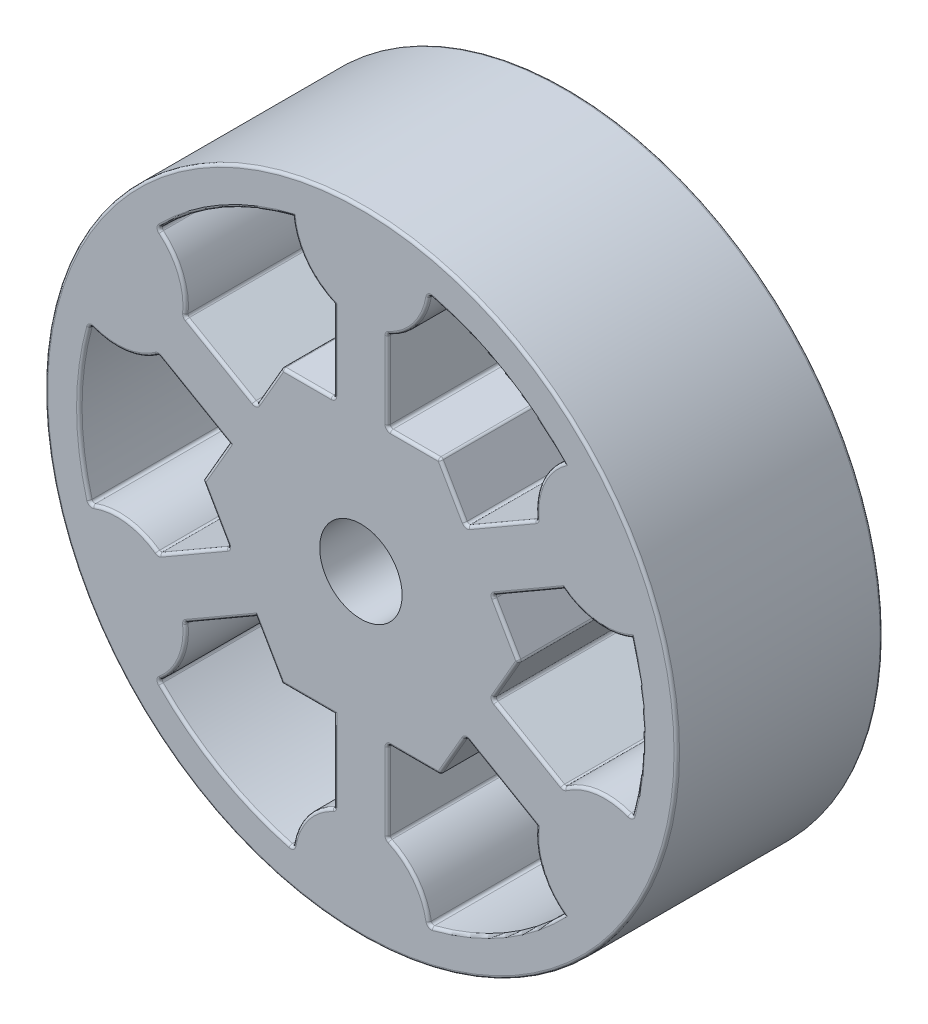
SolidWorks part; units mm, degrees
ref_plane "Front Plane" through (0, 0, 0) normal (0, 0, 1) x (1, 0, 0)
ref_plane "Top Plane" through (0, 0, 0) normal (0, 1, 0) x (1, 0, 0)
ref_plane "Right Plane" through (0, 0, 0) normal (1, 0, 0) x (0, 0, -1)
sketch "Sketch1" plane through (0, 0, 0) normal (0, 0, 1) x (1, 0, 0)
  line L0 (0, 1000) -> (0, -9.9593) construction
  line L1 (0, 0) -> (-7577.3498, 0) construction
  line L2 (-1.9562, 15.8986) -> (-1.9562, 9.9593)
  line L3 (11.5, 0) -> (9.6031, 3.2855)
  line L4 (5.75, 9.9593) -> (1.9562, 9.9593)
  line L5 (-5.75, 9.9593) -> (-7.6469, 6.6738)
  line L6 (-11.5, 0) -> (-9.6031, -3.2855)
  line L7 (-5.75, -9.9593) -> (-1.9562, -9.9593)
  line L8 (5.75, -9.9593) -> (7.6469, -6.6738)
  line L9 (1.9562, 15.8986) -> (1.9562, 9.9593)
  line L10 (14.7467, 6.2551) -> (9.6031, 3.2855)
  line L11 (12.7904, 9.6434) -> (7.6469, 6.6738)
  line L12 (5.75, -9.9593) -> (7.6469, -6.6738)
  line L13 (11.5, 0) -> (9.6031, 3.2855)
  line L14 (5.75, 9.9593) -> (1.9562, 9.9593)
  line L15 (-5.75, 9.9593) -> (-7.6469, 6.6738)
  line L16 (-11.5, 0) -> (-9.6031, -3.2855)
  line L17 (-5.75, -9.9593) -> (-1.9562, -9.9593)
  line L18 (12.7904, -9.6434) -> (7.6469, -6.6738)
  line L19 (14.7467, -6.2551) -> (9.6031, -3.2855)
  line L20 (-5.75, -9.9593) -> (-1.9562, -9.9593)
  line L21 (5.75, -9.9593) -> (7.6469, -6.6738)
  line L22 (11.5, 0) -> (9.6031, 3.2855)
  line L23 (5.75, 9.9593) -> (1.9562, 9.9593)
  line L24 (-5.75, 9.9593) -> (-7.6469, 6.6738)
  line L25 (-11.5, 0) -> (-9.6031, -3.2855)
  line L26 (-1.9562, -15.8986) -> (-1.9562, -9.9593)
  line L27 (1.9562, -15.8986) -> (1.9562, -9.9593)
  line L28 (-11.5, 0) -> (-9.6031, -3.2855)
  line L29 (-5.75, -9.9593) -> (-1.9562, -9.9593)
  line L30 (5.75, -9.9593) -> (7.6469, -6.6738)
  line L31 (11.5, 0) -> (9.6031, 3.2855)
  line L32 (5.75, 9.9593) -> (1.9562, 9.9593)
  line L33 (-5.75, 9.9593) -> (-7.6469, 6.6738)
  line L34 (-14.7467, -6.2551) -> (-9.6031, -3.2855)
  line L35 (-12.7904, -9.6434) -> (-7.6469, -6.6738)
  line L36 (-5.75, 9.9593) -> (-7.6469, 6.6738)
  line L37 (-11.5, 0) -> (-9.6031, -3.2855)
  line L38 (-5.75, -9.9593) -> (-1.9562, -9.9593)
  line L39 (5.75, -9.9593) -> (7.6469, -6.6738)
  line L40 (11.5, 0) -> (9.6031, 3.2855)
  line L41 (5.75, 9.9593) -> (1.9562, 9.9593)
  line L42 (-12.7904, 9.6434) -> (-7.6469, 6.6738)
  line L43 (-14.7467, 6.2551) -> (-9.6031, 3.2855)
  line L44 (5.75, 9.9593) -> (1.9562, 9.9593)
  line L45 (-5.75, 9.9593) -> (-7.6469, 6.6738)
  line L46 (-11.5, 0) -> (-9.6031, -3.2855)
  line L47 (-5.75, -9.9593) -> (-1.9562, -9.9593)
  line L48 (5.75, -9.9593) -> (7.6469, -6.6738)
  line L49 (11.5, 0) -> (9.6031, 3.2855)
  line L50 (-1.9562, 9.9593) -> (-5.75, 9.9593)
  line L51 (-1.9562, 9.9593) -> (-5.75, 9.9593)
  line L52 (-1.9562, 9.9593) -> (-5.75, 9.9593)
  line L53 (-1.9562, 9.9593) -> (-5.75, 9.9593)
  line L54 (-1.9562, 9.9593) -> (-5.75, 9.9593)
  line L55 (-1.9562, 9.9593) -> (-5.75, 9.9593)
  line L56 (-9.6031, 3.2855) -> (-11.5, 0)
  line L57 (-9.6031, 3.2855) -> (-11.5, 0)
  line L58 (-9.6031, 3.2855) -> (-11.5, 0)
  line L59 (-9.6031, 3.2855) -> (-11.5, 0)
  line L60 (-9.6031, 3.2855) -> (-11.5, 0)
  line L61 (-9.6031, 3.2855) -> (-11.5, 0)
  line L62 (-7.6469, -6.6738) -> (-5.75, -9.9593)
  line L63 (-7.6469, -6.6738) -> (-5.75, -9.9593)
  line L64 (-7.6469, -6.6738) -> (-5.75, -9.9593)
  line L65 (-7.6469, -6.6738) -> (-5.75, -9.9593)
  line L66 (-7.6469, -6.6738) -> (-5.75, -9.9593)
  line L67 (-7.6469, -6.6738) -> (-5.75, -9.9593)
  line L68 (1.9562, -9.9593) -> (5.75, -9.9593)
  line L69 (1.9562, -9.9593) -> (5.75, -9.9593)
  line L70 (1.9562, -9.9593) -> (5.75, -9.9593)
  line L71 (1.9562, -9.9593) -> (5.75, -9.9593)
  line L72 (1.9562, -9.9593) -> (5.75, -9.9593)
  line L73 (1.9562, -9.9593) -> (5.75, -9.9593)
  line L74 (0, -20.5) -> (0, -7577.3498) construction
  line L75 (9.6031, -3.2855) -> (11.5, 0)
  line L76 (9.6031, -3.2855) -> (11.5, 0)
  line L77 (9.6031, -3.2855) -> (11.5, 0)
  line L78 (9.6031, -3.2855) -> (11.5, 0)
  line L79 (9.6031, -3.2855) -> (11.5, 0)
  line L80 (9.6031, -3.2855) -> (11.5, 0)
  line L81 (7.6469, 6.6738) -> (5.75, 9.9593)
  line L82 (7.6469, 6.6738) -> (5.75, 9.9593)
  line L83 (7.6469, 6.6738) -> (5.75, 9.9593)
  line L84 (7.6469, 6.6738) -> (5.75, 9.9593)
  line L85 (7.6469, 6.6738) -> (5.75, 9.9593)
  line L86 (7.6469, 6.6738) -> (5.75, 9.9593)
  arc A0 (14.7441, 14.2429) -> (4.9627, 19.8902) centre (0, 0) ccw
  circle A1 centre (0, 0) radius 23
  arc A2 (-4.9627, 19.8902) -> (-14.7441, 14.2429) centre (0, 0) ccw
  arc A3 (-4.9627, 19.8902) -> (-1.9562, 15.8986) centre (0, 20.5) ccw
  arc A4 (1.9562, 15.8986) -> (4.9627, 19.8902) centre (0, 20.5) ccw
  arc A5 (14.7441, 14.2429) -> (12.7904, 9.6434) centre (17.7535, 10.25) ccw
  arc A6 (14.7467, 6.2551) -> (19.7068, 5.6473) centre (17.7535, 10.25) ccw
  arc A7 (19.7068, -5.6473) -> (14.7467, -6.2551) centre (17.7535, -10.25) ccw
  arc A8 (12.7904, -9.6434) -> (14.7441, -14.2429) centre (17.7535, -10.25) ccw
  arc A9 (4.9627, -19.8902) -> (1.9562, -15.8986) centre (0, -20.5) ccw
  arc A10 (-1.9562, -15.8986) -> (-4.9627, -19.8902) centre (0, -20.5) ccw
  arc A11 (-14.7441, -14.2429) -> (-12.7904, -9.6434) centre (-17.7535, -10.25) ccw
  arc A12 (-14.7467, -6.2551) -> (-19.7068, -5.6473) centre (-17.7535, -10.25) ccw
  arc A13 (-19.7068, 5.6473) -> (-14.7467, 6.2551) centre (-17.7535, 10.25) ccw
  arc A14 (-12.7904, 9.6434) -> (-14.7441, 14.2429) centre (-17.7535, 10.25) ccw
  arc A15 (19.7068, -5.6473) -> (19.7068, 5.6473) centre (0, 0) ccw
  arc A16 (4.9627, -19.8902) -> (14.7441, -14.2429) centre (0, 0) ccw
  arc A17 (-14.7441, -14.2429) -> (-4.9627, -19.8902) centre (0, 0) ccw
  arc A18 (-19.7068, 5.6473) -> (-19.7068, -5.6473) centre (0, 0) ccw
  circle A19 centre (0, 0) radius 3
  point P13 (-13.1515, 12.2048)
  point P90 (0, 0)
  dimension "D2" = 6
  dimension "D3" = 46
  dimension "D4" = 41
  dimension "D5" = 5
  dimension "D7" = 20.5
  dimension "D8" = 6
  dimension "D1" = 23
  dimension "D6" = 20.5
  dimension "D9" = 3.9125
  dimension "D10" = 5
extrude "Boss-Extrude1" add sketch "Sketch1" along normal mid plane 15 contours A1 A18 A13 L43 L56 L6 L34 A12 A17 A11 L35 L62 L7 L26 A10 A16 A9 L27 L68 L8 L18 A8 A15 A7 L19 L75 L3 L10 A6 A0 A5 L11 L81 L4 L9 A4 L42 A14 A2 A3 L2 L50 L5 region at (-22.3495, 0, 0)
fillet "Fillet1" radius 0.2 110 edges at (-12.1749, 4.7703, -7.5) (-10.5516, -1.6427, -7.5) (-10.2187, -8.1586, -7.5) (-1.9562, -12.9289, -7.5) (3.8531, -9.9593, -7.5) (10.2187, -8.1586, -7.5) (20.5, 0, -7.5) (12.1749, 4.7703, -7.5) (13.1515, 12.2048, -7.5) (10.25, 17.7535, -7.5) (-6.6984, 8.3165, -7.5) (-1.9562, 12.9289, -7.5) (-20.5, 0, -7.5) (-17.1454, 5.2871, -7.5) (-12.1749, -4.7703, -7.5) (-17.1454, -5.2871, -7.5) (-10.25, -17.7535, -7.5) (-13.1515, -12.2048, -7.5) (-3.9939, -17.4919, -7.5) (10.25, -17.7535, -7.5) (3.9939, -17.4919, -7.5) (1.9562, -12.9289, -7.5) (6.6984, -8.3165, -7.5) (17.1454, -5.2871, -7.5) (12.1749, -4.7703, -7.5) (10.5516, -1.6427, -7.5) (10.5516, 1.6427, -7.5) (23, 0, -7.5) (10.2187, 8.1586, -7.5) (6.6984, 8.3165, -7.5) (3.8531, 9.9593, -7.5) (1.9562, 12.9289, -7.5) (3.9939, 17.4919, -7.5) (-10.2187, 8.1586, -7.5) (-13.1515, 12.2048, -7.5) (-10.25, 17.7535, -7.5) (-3.8531, 9.9593, -7.5) (-20.5, 0, 7.5) (-17.1454, 5.2871, 7.5) (-12.1749, 4.7703, 7.5) (-10.5516, 1.6427, 7.5) (-10.5516, -1.6427, 7.5) (-12.1749, -4.7703, 7.5) (-17.1454, -5.2871, 7.5) (-10.25, -17.7535, 7.5) (-13.1515, -12.2048, 7.5) (-10.2187, -8.1586, 7.5) (-6.6984, -8.3165, 7.5) (-3.8531, -9.9593, 7.5) (-1.9562, -12.9289, 7.5) (-3.9939, -17.4919, 7.5) (10.25, -17.7535, 7.5) (3.9939, -17.4919, 7.5) (1.9562, -12.9289, 7.5) (3.8531, -9.9593, 7.5) (6.6984, -8.3165, 7.5) (10.2187, -8.1586, 7.5) (13.1515, -12.2048, 7.5) (20.5, 0, 7.5) (17.1454, -5.2871, 7.5) (12.1749, -4.7703, 7.5) (10.5516, -1.6427, 7.5) (10.5516, 1.6427, 7.5) (12.1749, 4.7703, 7.5) (17.1454, 5.2871, 7.5) (23, 0, 7.5) (10.25, 17.7535, 7.5) (13.1515, 12.2048, 7.5) (10.2187, 8.1586, 7.5) (6.6984, 8.3165, 7.5) (3.8531, 9.9593, 7.5) (1.9562, 12.9289, 7.5) (3.9939, 17.4919, 7.5) (-10.2187, 8.1586, 7.5) (-13.1515, 12.2048, 7.5) (-10.25, 17.7535, 7.5) (-3.9939, 17.4919, 7.5) (-1.9562, 12.9289, 7.5) (-3.8531, 9.9593, 7.5) (-6.6984, 8.3165, 7.5) (-19.7068, -5.6473, 0) (-14.7467, -6.2551, 0) (-9.6031, -3.2855, 0) (-14.7467, 6.2551, 0) (-19.7068, 5.6473, 0) (-4.9627, -19.8902, 0) (-1.9562, -15.8986, 0) (-12.7904, -9.6434, 0) (-14.7441, -14.2429, 0) (7.6469, -6.6738, 0) (5.75, -9.9593, 0) (1.9562, -9.9593, 0) (1.9562, -15.8986, 0) (4.9627, -19.8902, 0) (9.6031, 3.2855, 0) (11.5, 0, 0) (9.6031, -3.2855, 0) (14.7467, -6.2551, 0) (19.7068, -5.6473, 0) (4.9627, 19.8902, 0) (1.9562, 15.8986, 0) (1.9562, 9.9593, 0) (5.75, 9.9593, 0) (7.6469, 6.6738, 0) (12.7904, 9.6434, 0) (-7.6469, 6.6738, 0) (-5.75, 9.9593, 0) (-1.9562, 9.9593, 0) (-14.7441, 14.2429, 0) (-12.7904, 9.6434, 0)
